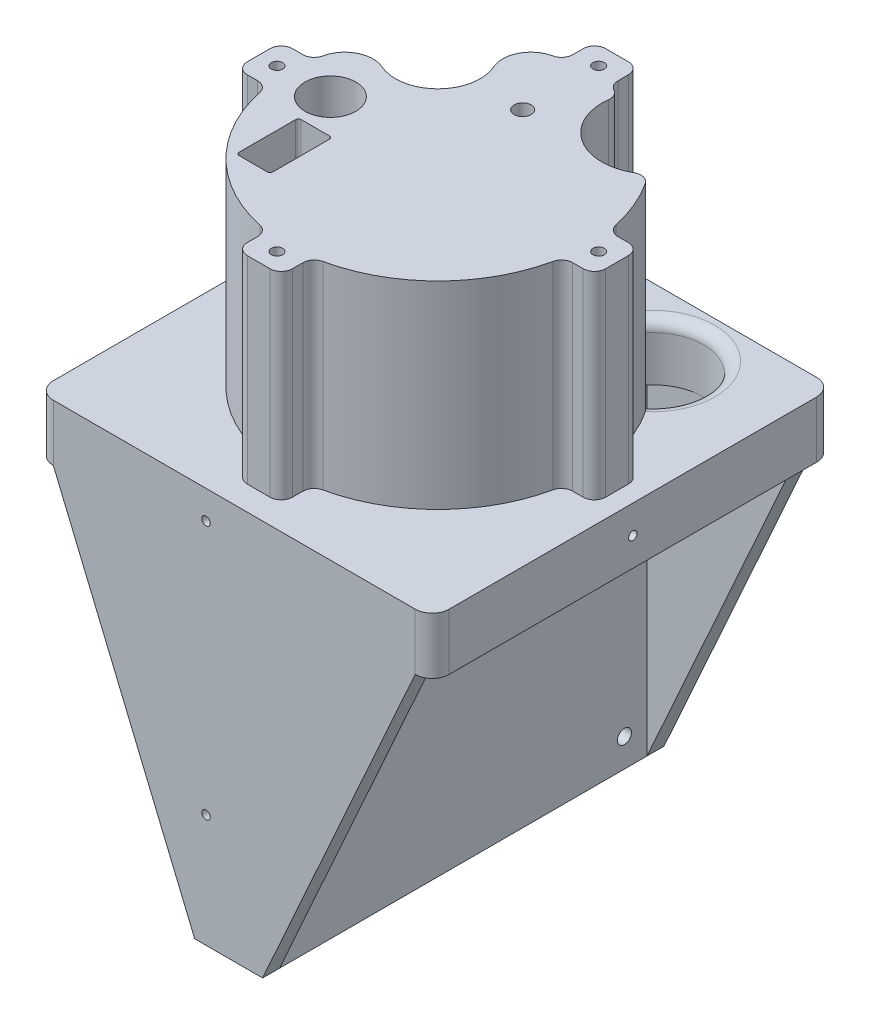
SolidWorks part; units mm, degrees
material "ABS"
ref_plane "Front Plane" through (0, 0, 0) normal (0, 0, 1) x (1, 0, 0)
ref_plane "Top Plane" through (0, 0, 0) normal (0, 1, 0) x (1, 0, 0)
ref_plane "Right Plane" through (0, 0, 0) normal (1, 0, 0) x (0, 0, -1)
sketch "Sketch1" plane through (0, 0, 0) normal (0, 1, 0) x (1, 0, 0)
  circle A0 centre (0, 0) radius 26.5
  dimension "D1" = 53
extrude "Boss-Extrude1" add sketch "Sketch1" along normal blind 35
sketch "Sketch2" plane through (0, 0, 0) normal (0, -1, 0) x (1, 0, 0)
  line L0 (0, 0) -> (0, 31.7947) construction
  line L1 (-4, 31.6964) -> (4, 31.6964)
  line L2 (-4, 31.6964) -> (-4, 26.1964)
  line L3 (4, 31.6964) -> (4, 26.1964)
  line L4 (4, 26.1964) -> (-4, 26.1964)
  line L5 (-4, 28.4464) -> (4, 28.4464) construction
  circle A0 centre (0, 0) radius 26.5 construction
  circle A1 centre (0, 28.4464) radius 1
  dimension "D4" = 2
  dimension "D1" = 8
  dimension "D2" = 5.5
  dimension "D3" = 3.25
extrude "Boss-Extrude2" add sketch "Sketch2" against normal blind 35
fillet "Fillet1" radius 2 4 edges at (4, 17.5, 26.1964) (4, 17.5, 31.6964) (-4, 17.5, 26.1964) (-4, 17.5, 31.6964)
pattern_circular "CirPattern1" count 4 over 360 about axis through (0, 35, 0) along (0, 1, 0) of "Boss-Extrude2", "Fillet1"
sketch "Sketch4" plane through (0, 0, 0) normal (0, 1, 0) x (1, 0, 0)
  line L0 (14, 32) -> (14, 16) construction
  line L1 (-32, 35) -> (32, 35)
  line L2 (14, 16) -> (-16, 16) construction
  line L5 (35, 32) -> (35, -33)
  line L6 (-32, 0) -> (0, 0)
  line L7 (-32, 0) -> (-32, 32)
  line L8 (-32, 32) -> (0, 32)
  line L9 (0, 0) -> (0, 32)
  line L10 (-32, 0) -> (0, 32) construction
  line L11 (-32, 32) -> (0, 0) construction
  line L12 (-35, 32) -> (-35, -33)
  line L13 (-32, -36) -> (32, -36)
  line L14 (4, -33) -> (24, -33)
  line L15 (4, -33) -> (4, 32)
  line L16 (4, 32) -> (24, 32)
  line L17 (24, -33) -> (24, 32)
  line L18 (4, -33) -> (24, 32) construction
  line L19 (4, 32) -> (24, -33) construction
  arc A1 (-32, -36) -> (-35, -33) centre (-32, -33) cw
  arc A2 (-35, 32) -> (-32, 35) centre (-32, 32) cw
  arc A4 (32, -36) -> (35, -33) centre (32, -33) ccw
  arc A5 (32, 35) -> (35, 32) centre (32, 32) cw
  point P9 (-35, -36)
  point P23 (-35, 35)
  dimension "D9" = 3
  dimension "D1" = 71
  dimension "D2" = 20
  dimension "D3" = 32
  dimension "D4" = 32
  dimension "D5" = 35
  dimension "D6" = 65
  dimension "D7" = 16
  dimension "D8" = 30
  dimension "D10" = 3
  dimension "D12" = 3
extrude "Boss-Extrude4" add sketch "Sketch4" against normal blind 10 contours L13 A4 L5 A5 L1 A2 L12 A1
sketch "Sketch7" plane through (0, 35, 0) normal (0, 1, 0) x (1, 0, 0)
  line L0 (0, 0) -> (0, 15) construction
  circle A0 centre (0, 15) radius 1.5
  dimension "D1" = 3
  dimension "D2" = 15
extrude "Cut-Extrude2" cut sketch "Sketch7" against normal blind 3
sketch "Sketch8" plane through (0, -10, 0) normal (0, -1, 0) x (1, 0, 0)
  line L0 (0, 0) -> (-16, 0) construction
  line L1 (-16, 0) -> (-16, -16) construction
  line L5 (5, 36) -> (5, -35)
  line L6 (5, -35) -> (-7, -35)
  line L9 (-32, -35) -> (32, -35) construction
  line L12 (-32, 36) -> (32, 36) construction
  line L18 (-7, 36) -> (5, 36)
  line L19 (-16, -26) -> (-16, -35) construction
  line L23 (-16, -6) -> (-7, -6)
  line L24 (-16, -26) -> (-7, -26)
  line L26 (-7, 36) -> (-7, -6)
  line L27 (-7, -26) -> (-7, -35)
  arc A0 (-16, -6) -> (-16, -26) centre (-16, -16) ccw
  point P13 (-1, -35)
  dimension "D3" = 20
  dimension "D1" = 16
  dimension "D2" = 16
  dimension "D4" = 12
  dimension "D5" = 12
  dimension "D6" = 5
extrude "Boss-Extrude7" add sketch "Sketch8" along normal blind 10
sketch "Sketch3" plane through (0, 35, 0) normal (0, 1, 0) x (1, 0, 0)
  line L0 (0, 0) -> (-28.4464, 0) construction
  line L1 (-19, 0) -> (-15.5663, -6.1) construction
  line L2 (-15.5663, -6.1) -> (-15.5663, 0) construction
  line L4 (-18.0663, -6.1) -> (-13.0663, -6.1)
  line L5 (-18.5663, -6.6) -> (-18.5663, -16.6)
  line L6 (-18.0663, -17.1) -> (-13.0663, -17.1)
  line L7 (-12.5663, -6.6) -> (-12.5663, -16.6)
  circle A0 centre (-19, 0) radius 4.5
  arc A1 (-18.5663, -16.6) -> (-18.0663, -17.1) centre (-18.0663, -16.6) ccw
  arc A2 (-13.0663, -17.1) -> (-12.5663, -16.6) centre (-13.0663, -16.6) ccw
  arc A3 (-12.5663, -6.6) -> (-13.0663, -6.1) centre (-13.0663, -6.6) ccw
  arc A4 (-18.0663, -6.1) -> (-18.5663, -6.6) centre (-18.0663, -6.6) ccw
  point P12 (-15.5663, -6.1)
  point P15 (-18.5663, -17.1)
  point P20 (-12.5663, -6.1)
  point P23 (-18.5663, -6.1)
  dimension "D6" = 9
  dimension "D7" = 0.5
  dimension "D1" = 19
  dimension "D2" = 7
  dimension "D3" = 6.1
  dimension "D4" = 6
  dimension "D5" = 11
extrude "Cut-Extrude4" cut sketch "Sketch3" against normal up to next
sketch "Sketch13" plane through (0, -20, 0) normal (0, -1, 0) x (1, 0, 0)
  line L0 (-7, 36) -> (5, 36)
  line L1 (-32, 0) -> (-7, 0)
  line L2 (-32, 0) -> (-32, -32)
  line L3 (-32, -32) -> (-7, -32)
  line L5 (-32, 0) -> (0, -32) construction
  line L6 (-32, -32) -> (0, 0) construction
  line L7 (5, 36) -> (5, -35)
  line L8 (5, -35) -> (-7, -35)
  line L9 (-7, -35) -> (-7, -32)
  line L10 (-7, -26) -> (-7, -35) construction
  line L11 (-7, 0) -> (-7, 36)
  line L12 (-7, 36) -> (-7, -6) construction
  line L13 (0, 0) -> (0, -32) construction
  line L14 (0, 0) -> (-7, 0) construction
  line L15 (0, -32) -> (-7, -32) construction
  point P0 (-16, -16)
  point P18 (-3.5, 0)
  dimension "D1" = 32
  dimension "D2" = 32
extrude "Boss-Extrude15" add sketch "Sketch13" along normal blind 10
sketch "Sketch32" plane through (0, -30, 0) normal (0, -1, 0) x (1, 0, 0)
  line L0 (0, 0) -> (-7, 0) construction
  line L1 (0, 0) -> (0, -32) construction
  line L2 (-32, -32) -> (0, 0) construction
  line L3 (0, -32) -> (-7, -32) construction
  circle A4 centre (-16, -16) radius 7.5
  point P1 (-16, -16)
  dimension "D1" = 15
extrude "Cut-Extrude5" cut sketch "Sketch32" against normal through all
sketch "Sketch33" plane through (0, -30, 0) normal (0, -1, 0) x (1, 0, 0)
  line L0 (5, 36) -> (-7, 36)
  line L1 (-7, 36) -> (-7, 0)
  line L2 (-7, 0) -> (0, 0)
  line L3 (0, 0) -> (0, -32)
  line L6 (5, -35) -> (5, 36)
  line L7 (-7, -32) -> (0, -32)
  line L8 (5, -35) -> (-7, -35)
  line L17 (-32, 0) -> (-32, -32)
  line L18 (-32, -32) -> (-7, -32)
  line L19 (-7, -32) -> (-7, -35)
  line L20 (-7, -35) -> (5, -35)
  line L21 (5, -35) -> (5, 36)
  line L22 (5, 36) -> (-7, 36)
  line L23 (-7, 36) -> (-7, 0)
  line L24 (-7, 0) -> (-32, 0)
  line L27 (-7, -32) -> (-7, -35)
  dimension "D1" = 0
extrude "Boss-Extrude16" add sketch "Sketch33" along normal blind 40
sketch "Sketch34" plane through (0, 0, 36) normal (0, 0, 1) x (1, 0, 0)
  line L0 (-32, -10) -> (-7, -70)
  line L1 (-7, -70) -> (-7, -10)
  line L2 (-7, -10) -> (-32, -10)
  line L3 (5, -10) -> (32, -10)
  line L4 (32, -10) -> (5, -70)
  line L5 (5, -70) -> (5, -10)
extrude "Boss-Extrude17" add sketch "Sketch34" against normal blind 3
ref_plane "Plane1" through (0, 0, 0.5) normal (0, 0, 1) x (1, 0, 0)
mirror "Mirror1" about plane through (0, 0, 0.5) normal (0, 0, 1) of "Boss-Extrude17"
sketch "Sketch36" plane through (5, 0, 0) normal (1, 0, 0) x (0, 0, -1)
  line L0 (32, -70) -> (-33, -70) construction
  line L1 (32, -10) -> (32, -70) construction
  circle A0 centre (28, -65) radius 1.25
  circle A1 centre (-29, -25) radius 1.25
  dimension "2.1" = 2.5
  dimension "D1" = 5
  dimension "D2" = 4
  dimension "D4" = 40
  dimension "D5" = 57
extrude "Cut-Extrude6" cut sketch "Sketch36" against normal up to next
sketch "Sketch38" plane through (0, 0, -35) normal (0, 0, -1) x (-1, 0, 0)
  circle A0 centre (5, -5) radius 0.75
  circle A1 centre (5, -50) radius 0.75
  dimension "D1" = 1.5
extrude "Cut-Extrude8" cut sketch "Sketch38" against normal blind 2
sketch "Sketch39" plane through (0, 0, 36) normal (0, 0, 1) x (1, 0, 0)
  circle A0 centre (-5, -5) radius 0.75
  circle A1 centre (-5, -50) radius 0.75
  dimension "D1" = 1.5
extrude "Cut-Extrude9" cut sketch "Sketch39" against normal blind 2
sketch "Sketch40" plane through (0, 0, 0) normal (0, 1, 0) x (1, 0, 0)
  circle A0 centre (0, -28.4464) radius 0.875
  dimension "D1" = 1.75
extrude "Cut-Extrude10" cut sketch "Sketch40" against normal blind 3
pattern_circular "CirPattern2" count 4 every 90 about axis through (0, 35, 0) along (0, 1, 0) of "Cut-Extrude10"
sketch "Sketch41" plane through (35, 0, 0) normal (1, 0, 0) x (0, 0, -1)
  circle A0 centre (-0.5, -5) radius 0.75
  dimension "D1" = 1.5
extrude "Cut-Extrude11" cut sketch "Sketch41" against normal blind 2
mirror "Mirror2" about plane through (0, 0, 0) normal (1, 0, 0) of "Cut-Extrude11"
fillet "Fillet4" radius 5 3 edges at (-22.9662, 17.5, -13.2213) (-21.3033, 0, -21.3033) (-13.2213, 17.5, -22.9662)
sketch "Sketch43" plane through (0, -30, 0) normal (0, -1, 0) x (1, 0, 0)
  line L0 (-29.5, -2.5) -> (-29.5, -29.5) construction
  line L1 (-32, 0) -> (0, 0) construction
  line L2 (-32, 0) -> (-32, -32) construction
  line L3 (-32, -32) -> (0, -32) construction
  line L4 (0, 0) -> (0, -32) construction
  line L5 (-32, 0) -> (0, -32) construction
  line L6 (-32, -32) -> (0, 0) construction
  line L7 (-29.5, -29.5) -> (-2.5, -29.5) construction
  line L8 (-2.5, -29.5) -> (-2.5, -2.5) construction
  line L9 (-2.5, -2.5) -> (-29.5, -2.5) construction
  circle A0 centre (-29.5, -2.5) radius 0.75
  circle A1 centre (-2.5, -2.5) radius 0.75
  circle A2 centre (-2.5, -29.5) radius 0.75
  circle A3 centre (-29.5, -29.5) radius 0.75
  point P0 (-16, -16)
  dimension "D1" = 1.5
  dimension "D2" = 2.5
extrude "Cut-Extrude12" cut sketch "Sketch43" against normal blind 3
fillet "Fillet7" radius 10 3 edges at (-11.5, -20, -26) (-11.5, -20, -6) (-26, -20, -16)
sketch "Sketch44" plane through (-7, 0, 0) normal (-1, 0, 0) x (0, 0, 1)
  circle A0 centre (29, -25) radius 3
  dimension "D1" = 6
extrude "Cut-Extrude13" cut sketch "Sketch44" against normal blind 7
sketch "Sketch45" plane through (0, -10, 0) normal (0, -1, 0) x (1, 0, 0)
  line L0 (5, 33) -> (5, -32) construction
  line L1 (5, -32) -> (25, -32) construction
  line L2 (5, -32) -> (32, -32) construction
  line L3 (25, -32) -> (25, 33) construction
  line L4 (32, 33) -> (5, 33) construction
  line L5 (25, 33) -> (5, 33) construction
  line L6 (15, -32) -> (15, 33) construction
  circle A0 centre (15, -23) radius 9
  dimension "D3" = 18
  dimension "D1" = 20
  dimension "D2" = 9
extrude "Cut-Extrude14" cut sketch "Sketch45" against normal through all
fillet "Fillet8" radius 2 3 edges at (19.9164, 0, -30.5385) (20.9411, 17.5, -16.2395) (6.418, 17.5, -25.7111)
sketch "Sketch46" plane through (0, 0, 0) normal (-1, 0, 0) x (0, 0, 1)
  circle A0 centre (-28, -65) radius 3
  dimension "D1" = 6
extrude "Cut-Extrude15" cut sketch "Sketch46" against normal blind 3
fillet "Fillet13" radius 2 4 edges at (0, -50, -32) (0, -50, 0) (-32, -25, -32) (-32, -25, 0)
